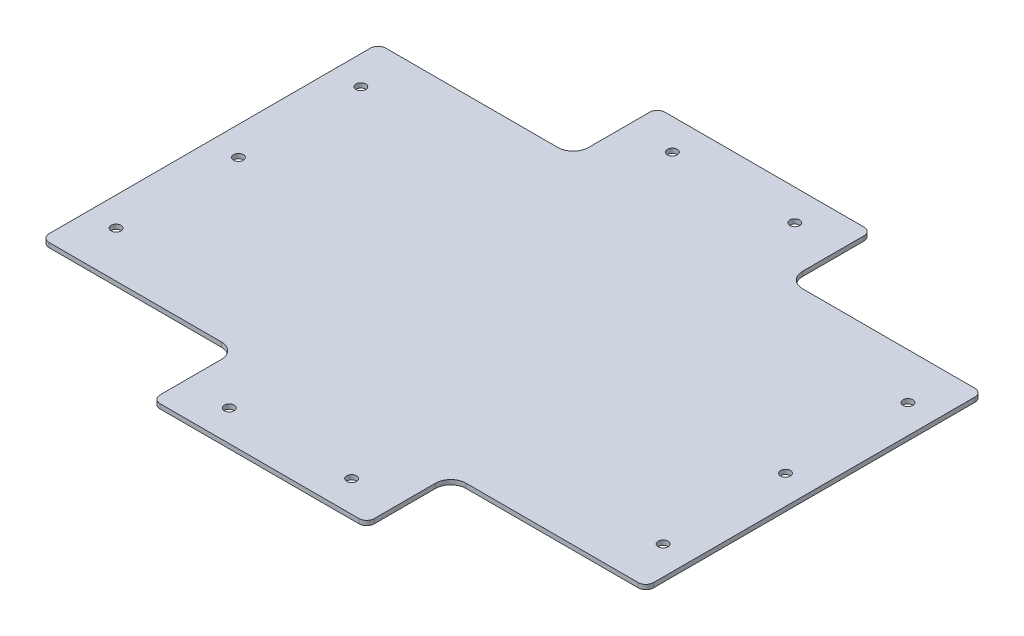
SolidWorks part; units mm, degrees
material "7075-T6, Пластина (SS)"
ref_plane "Спереди" through (0, 0, 0) normal (0, 0, 1) x (1, 0, 0)
ref_plane "Сверху" through (0, 0, 0) normal (0, 1, 0) x (1, 0, 0)
ref_plane "Справа" through (0, 0, 0) normal (1, 0, 0) x (0, 0, -1)
sketch "Эскиз1" plane through (0, 0, 0) normal (0, 1, 0) x (1, 0, 0)
  line L1 (-65, -165) -> (65, -165)
  line L2 (-197.5, -105) -> (-197.5, 105)
  line L3 (-65, 165) -> (65, 165)
  line L4 (197.5, -105) -> (197.5, 105)
  line L5 (-236.4266, 144.4996) -> (-147.9018, 144.4996) construction
  line L6 (-147.9018, 144.4996) -> (286.4952, 144.4996) construction
  line L18 (-284.5497, 0) -> (284.3305, 0) construction
  line L19 (-160.9018, 110) -> (-134.9018, 110)
  line L20 (-160.9018, 110) -> (-160.9018, 0)
  line L21 (-160.9018, 0) -> (-134.9018, 0)
  line L22 (-134.9018, 110) -> (-134.9018, 0)
  line L23 (-147.9018, -182.6295) -> (-147.9018, 219.9923) construction
  line L24 (-160.9018, 0) -> (-134.9018, 0)
  line L25 (-160.9018, 0) -> (-160.9018, -110)
  line L26 (-160.9018, -110) -> (-134.9018, -110)
  line L27 (-134.9018, 0) -> (-134.9018, -110)
  line L28 (-82.9018, -119.4996) -> (-212.9018, -119.4996)
  line L29 (-82.9018, 169.4996) -> (-212.9018, 169.4996)
  line L30 (-82.9018, 169.4996) -> (-82.9018, 119.4996)
  line L31 (-82.9018, 119.4996) -> (-212.9018, 119.4996)
  line L32 (-212.9018, 169.4996) -> (-212.9018, 119.4996)
  line L33 (-82.9018, 169.4996) -> (-212.9018, 119.4996) construction
  line L34 (-82.9018, 119.4996) -> (-212.9018, 169.4996) construction
  line L35 (-212.9018, -169.4996) -> (-212.9018, -119.4996)
  line L36 (-82.9018, -169.4996) -> (-212.9018, -169.4996)
  line L37 (-82.9018, -169.4996) -> (-82.9018, -119.4996)
  line L39 (-70, 120) -> (-70, 160)
  line L40 (0, 262.7398) -> (0, -186.5795) construction
  line L41 (-192.5, 110) -> (-80, 110)
  line L43 (-192.5, -110) -> (-80, -110)
  line L44 (-70, -120) -> (-70, -160)
  line L45 (70, 120) -> (70, 160)
  line L46 (192.5, 110) -> (80, 110)
  line L47 (192.5, -110) -> (80, -110)
  line L48 (70, -120) -> (70, -160)
  line L49 (82.9018, -169.4996) -> (82.9018, -119.4996)
  line L50 (82.9018, -169.4996) -> (212.9018, -169.4996)
  line L51 (212.9018, -169.4996) -> (212.9018, -119.4996)
  line L52 (82.9018, -119.4996) -> (212.9018, -119.4996)
  line L53 (160.9018, 0) -> (160.9018, -110)
  line L54 (160.9018, -110) -> (134.9018, -110)
  line L55 (134.9018, 0) -> (134.9018, -110)
  line L56 (160.9018, 0) -> (134.9018, 0)
  line L57 (160.9018, 110) -> (160.9018, 0)
  line L58 (160.9018, 0) -> (134.9018, 0)
  line L59 (134.9018, 110) -> (134.9018, 0)
  line L60 (160.9018, 110) -> (134.9018, 110)
  line L61 (82.9018, 119.4996) -> (212.9018, 119.4996)
  line L62 (212.9018, 169.4996) -> (212.9018, 119.4996)
  line L63 (82.9018, 169.4996) -> (212.9018, 169.4996)
  line L64 (82.9018, 169.4996) -> (82.9018, 119.4996)
  line L65 (40, -144.8055) -> (-40, -144.8055) construction
  line L66 (-178.7687, -80) -> (-178.7687, 80) construction
  arc A0 (70, -120) -> (80, -110) centre (80, -120) cw
  arc A1 (70, 120) -> (80, 110) centre (80, 120) ccw
  arc A2 (-80, -110) -> (-70, -120) centre (-80, -120) cw
  arc A3 (-70, 120) -> (-80, 110) centre (-80, 120) cw
  arc A4 (192.5, -110) -> (197.5, -105) centre (192.5, -105) ccw
  arc A5 (70, -160) -> (65, -165) centre (65, -160) cw
  arc A6 (-70, -160) -> (-65, -165) centre (-65, -160) ccw
  arc A7 (-192.5, -110) -> (-197.5, -105) centre (-192.5, -105) cw
  arc A8 (-192.5, 110) -> (-197.5, 105) centre (-192.5, 105) ccw
  arc A9 (197.5, 105) -> (192.5, 110) centre (192.5, 105) ccw
  arc A10 (70, 160) -> (65, 165) centre (65, 160) ccw
  arc A11 (-70, 160) -> (-65, 165) centre (-65, 160) cw
  circle A12 centre (40, 144.8055) radius 3.2
  circle A13 centre (40, -144.8055) radius 3.2
  circle A14 centre (-40, -144.8055) radius 3.2
  circle A15 centre (-40, 144.8055) radius 3.2
  circle A16 centre (-178.7687, 80) radius 3.2
  circle A17 centre (-178.7687, -80) radius 3.2
  circle A18 centre (-178.7687, 0) radius 3.2
  circle A19 centre (178.7687, 80) radius 3.2
  circle A20 centre (178.7687, 0) radius 3.2
  circle A21 centre (178.7687, -80) radius 3.2
  point P0 (0, 0)
  point P3 (70, -110)
  point P17 (-147.9018, 110)
  point P18 (-147.9018, 110)
  point P20 (-147.9018, 0)
  point P22 (-150, 134)
  point P37 (-147.9018, 144.4996)
  point P46 (70, 110)
  point P52 (-70, -110)
  point P55 (-70, 110)
  point P56 (-147.9018, 0)
  point P58 (0, 0)
  point P59 (-178.7687, 0)
  point P62 (178.7687, 80)
  point P77 (197.5, -110)
  point P80 (70, -165)
  point P83 (-70, -165)
  point P86 (-197.5, -110)
  point P89 (-197.5, 110)
  point P92 (197.5, 110)
  point P95 (70, 165)
  point P98 (-70, 165)
  point P99 (178.7687, 0)
  point P100 (40, 144.8055)
  point P101 (178.7687, -80)
  point P103 (-40, 144.8055)
  point P110 (0, 0)
  point P111 (0, 0)
  dimension "D2" = 50
  dimension "D6" = 10
  dimension "D11" = 40
  dimension "D12" = 40
  dimension "D4" = 5
  dimension "D17" = 425.8037
  dimension "D9" = 6.4
  dimension "D3" = 26
  dimension "D5" = 330
  dimension "D7" = 395
  dimension "D8" = 110
  dimension "D10" = 130
  dimension "D13" = 9.4996
  dimension "D14" = 12.9018
  dimension "D15" = 80
  dimension "D16" = 80
  dimension "D18" = 18.7313
  dimension "D19" = 20.1945
sketch "Эскиз2" plane through (0, 0, 0) normal (0, 1, 0) x (1, 0, 0)
  line L0 (-162.9105, 114) -> (-136.9105, 114)
  line L1 (-162.9105, 114) -> (-162.9105, 0)
  line L2 (-162.9105, 0) -> (-136.9105, 0)
  line L3 (-136.9105, 114) -> (-136.9105, 0)
  line L4 (-149.9105, -192.6295) -> (-149.9105, 209.9923) construction
  line L5 (-162.9105, 0) -> (-136.9105, 0)
  line L6 (-162.9105, 0) -> (-162.9105, -114)
  line L7 (-162.9105, -114) -> (-136.9105, -114)
  line L8 (-136.9105, 0) -> (-136.9105, -114)
  line L9 (-99.9105, -123.5568) -> (-199.9105, -123.5568)
  line L10 (-99.9105, 163.4996) -> (-199.9105, 163.4996)
  line L11 (-99.9105, 163.4996) -> (-99.9105, 123.4996)
  line L12 (-99.9105, 123.4996) -> (-199.9105, 123.4996)
  line L13 (-199.9105, 163.4996) -> (-199.9105, 123.4996)
  line L14 (-199.9105, -163.5568) -> (-199.9105, -123.5568)
  line L15 (-99.9105, -163.5568) -> (-199.9105, -163.5568)
  line L16 (-99.9105, -163.5568) -> (-99.9105, -123.5568)
  line L17 (-284.5497, 0) -> (284.3305, 0) construction
  point P11 (-149.9105, 0)
  point P12 (-149.9105, 0)
sketch "Эскиз3" plane through (0, 0, 0) normal (0, 1, 0) x (1, 0, 0)
  line L0 (-89.8176, -177.9027) -> (70.2405, -177.9027)
  line L1 (-209.7886, -106.9112) -> (-209.7886, 106.8353)
  line L2 (-80.029, 172.0973) -> (50.2405, 172.0973)
  line L3 (170.2114, -106.9112) -> (170.2114, 103.9123)
  line L4 (-87.1938, 124.0033) -> (-87.1938, 164.9326)
  line L5 (-202.6239, 114) -> (-97.1971, 114)
  line L6 (-202.6239, -114.076) -> (-106.9857, -114.076)
  line L7 (-96.9823, -124.0793) -> (-96.9823, -170.738)
  line L8 (57.4052, 121.0803) -> (57.4052, 164.9326)
  line L9 (163.0467, 111.077) -> (67.4085, 111.077)
  line L10 (163.0467, -114.076) -> (87.4085, -114.076)
  line L11 (77.4052, -124.0793) -> (77.4052, -170.738)
  line L13 (-162.9105, 114) -> (-136.9105, 114) construction
  arc A0 (77.4052, -124.0793) -> (87.4085, -114.076) centre (87.4085, -124.0793) cw
  arc A1 (57.4052, 121.0803) -> (67.4085, 111.077) centre (67.4085, 121.0803) ccw
  arc A2 (-106.9857, -114.076) -> (-96.9823, -124.0793) centre (-106.9857, -124.0793) cw
  arc A3 (-87.1938, 124.0033) -> (-97.1971, 114) centre (-97.1971, 124.0033) cw
  arc A4 (-80.029, 172.0973) -> (-87.1938, 164.9326) centre (-80.029, 164.9326) ccw
  arc A5 (50.2405, 172.0973) -> (57.4052, 164.9326) centre (50.2405, 164.9326) cw
  arc A6 (170.2114, 103.9123) -> (163.0467, 111.077) centre (163.0467, 103.9123) ccw
  arc A7 (170.2114, -106.9112) -> (163.0467, -114.076) centre (163.0467, -106.9112) cw
  arc A8 (70.2405, -177.9027) -> (77.4052, -170.738) centre (70.2405, -170.738) ccw
  arc A9 (-89.8176, -177.9027) -> (-96.9823, -170.738) centre (-89.8176, -170.738) cw
  arc A10 (-209.7886, -106.9112) -> (-202.6239, -114.076) centre (-202.6239, -106.9112) ccw
  arc A11 (-209.7886, 106.8353) -> (-202.6239, 114) centre (-202.6239, 106.8353) cw
  point P36 (115.2276, 111.077)
  point P39 (-149.9105, 114)
  point P42 (-149.9105, 114)
  dimension "D3" = 10.0033
  dimension "D4" = 7.1647
  dimension "D1" = 380
  dimension "D2" = 350
  dimension "D5" = 112.8062
  dimension "D6" = 63.8267
  dimension "D7" = 61.0203
extrude "Бобышка-Вытянуть1" add sketch "Эскиз1" along normal blind 3 separate body contours A11 L39 A3 L41 L22 L27 L43 A2 L44 A6 L1 A5 L48 A0 L47 L55 L59 L46 A1 L45 A10 L3 | L4 A9 L46 L57 L53 L47 A4 | L46 L59 L56 L57 | L53 L56 L55 L47 | L27 L21 L25 L26 | L41 A8 L2 A7 L43 L25 L20 | L22 L19 L20 L21 region at (0, 0, 0) region at (-147.9018, 0, 55) region at (147.9018, 0, 55) region at (-176.7009, 0, 107.7698) region at (-147.9018, 0, -55) region at (163.1321, 0, 55) region at (147.9018, 0, -55)
